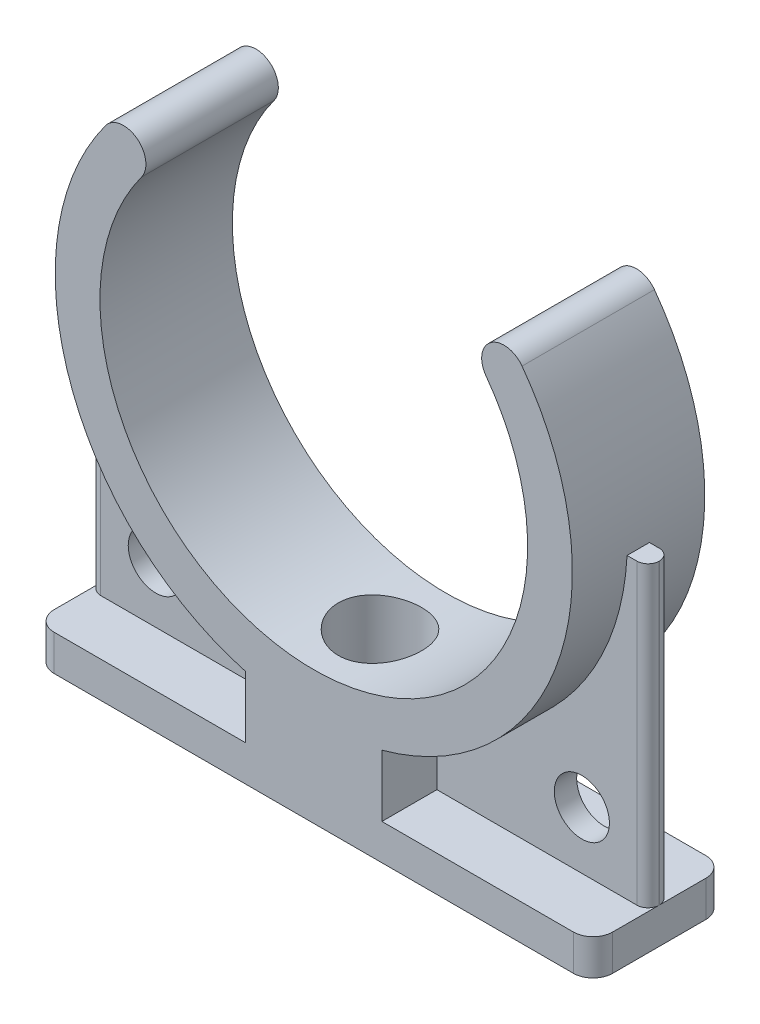
SolidWorks part; units mm, degrees
ref_plane "Front Plane" through (0, 0, 0) normal (0, 0, 1) x (1, 0, 0)
ref_plane "Top Plane" through (0, 0, 0) normal (0, 1, 0) x (1, 0, 0)
ref_plane "Right Plane" through (0, 0, 0) normal (1, 0, 0) x (0, 0, -1)
ref_plane "Plane1" through (0, 0, -1.5875) normal (0, 0, -1) x (-1, 0, 0)
sketch "Sketch1" plane through (0, 0, -1.5875) normal (0, 0, -1) x (-1, 0, 0)
  line L0 (-36.6548, 47.371) -> (36.6548, 47.371)
  arc A0 (36.6548, 47.371) -> (-36.6548, 47.371) centre (0, 49.2507) ccw
extrude "Boss-Extrude1" add sketch "Sketch1" against normal blind 3.175
sketch "Sketch2" plane through (0, 47.371, 0) normal (0, -1, 0) x (1, 0, 0)
  line L0 (36.6548, -1.5875) -> (-36.6548, -1.5875)
  line L1 (-36.6548, -1.5875) -> (-36.6548, 1.5875)
  line L2 (-36.6548, 1.5875) -> (36.6548, 1.5875)
  line L3 (36.6548, 1.5875) -> (36.6548, -1.5875)
extrude "Boss-Extrude2" add sketch "Sketch2" along normal blind 33.528
sketch "Sketch3" plane through (0, 0, -1.5875) normal (0, 0, -1) x (-1, 0, 0)
  line L0 (9.6647, 13.843) -> (-9.6647, 13.843)
  arc A0 (-9.6647, 13.843) -> (9.6647, 13.843) centre (0, 49.2507) cw
extrude "Boss-Extrude3" add sketch "Sketch3" along normal blind 7.8105
sketch "Sketch4" plane through (-36.6548, 0, 0) normal (-1, 0, 0) x (0, 0, 1)
  line L0 (-1.5875, 13.843) -> (-1.5875, 47.371)
  line L1 (-1.5875, 47.371) -> (1.5875, 47.371)
  line L2 (1.5875, 47.371) -> (1.5875, 13.843)
  line L3 (1.5875, 13.843) -> (-1.5875, 13.843)
extrude "Boss-Extrude4" add sketch "Sketch4" along normal blind 2.9819
sketch "Sketch5" plane through (36.6548, 0, 0) normal (1, 0, 0) x (0, 0, -1)
  line L0 (-1.5875, 13.843) -> (-1.5875, 47.371)
  line L1 (-1.5875, 47.371) -> (1.5875, 47.371)
  line L2 (1.5875, 47.371) -> (1.5875, 13.843)
  line L3 (1.5875, 13.843) -> (-1.5875, 13.843)
extrude "Boss-Extrude5" add sketch "Sketch5" along normal blind 2.9819
sketch "Sketch6" plane through (0, 13.843, 0) normal (0, -1, 0) x (1, 0, 0)
  line L0 (-39.6367, 1.5875) -> (39.6367, 1.5875)
  line L1 (39.6367, 1.5875) -> (39.6367, -9.398)
  line L2 (39.6367, -9.398) -> (-39.6367, -9.398)
  line L3 (-39.6367, -9.398) -> (-39.6367, 1.5875)
extrude "Boss-Extrude6" add sketch "Sketch6" along normal blind 13.843
sketch "Sketch7" plane through (0, 13.843, 0) normal (0, 1, 0) x (-1, 0, 0)
  line L0 (-39.6367, -1.5875) -> (-39.6367, -9.398)
  line L1 (-39.6367, -9.398) -> (-9.6647, -9.398)
  line L2 (-9.6647, -9.398) -> (-9.6647, -1.5875)
  line L3 (-9.6647, -1.5875) -> (-39.6367, -1.5875)
extrude "Cut-Extrude1" cut sketch "Sketch7" against normal blind 8.763
sketch "Sketch8" plane through (0, 13.843, 0) normal (0, 1, 0) x (-1, 0, 0)
  line L0 (9.6647, -9.398) -> (39.6367, -9.398)
  line L1 (39.6367, -9.398) -> (39.6367, -1.5875)
  line L2 (39.6367, -1.5875) -> (9.6647, -1.5875)
  line L3 (9.6647, -1.5875) -> (9.6647, -9.398)
extrude "Cut-Extrude2" cut sketch "Sketch8" against normal blind 8.763
sketch "Sketch9" plane through (0, 0, 1.5875) normal (0, 0, 1) x (1, 0, 0)
  line L0 (9.6647, 13.843) -> (9.6647, 5.08)
  line L1 (9.6647, 5.08) -> (39.6367, 5.08)
  line L2 (39.6367, 5.08) -> (39.6367, 0)
  line L3 (39.6367, 0) -> (-39.6367, 0)
  line L4 (-39.6367, 0) -> (-39.6367, 5.08)
  line L5 (-39.6367, 5.08) -> (-9.6647, 5.08)
  line L6 (-9.6647, 5.08) -> (-9.6647, 13.843)
  arc A0 (-9.6647, 13.843) -> (9.6647, 13.843) centre (0, 49.2507) cw
extrude "Boss-Extrude7" add sketch "Sketch9" along normal blind 7.8105
sketch "Sketch10" plane through (0, 0, 9.398) normal (0, 0, 1) x (1, 0, 0)
  arc A0 (-29.562, 71.0037) -> (-24.4475, 67.2402) centre (-27.0048, 69.122) cw
  arc A1 (-24.4475, 67.2402) -> (24.4475, 67.2402) centre (0, 49.2507) cw
  arc A2 (24.4475, 67.2402) -> (29.562, 71.0037) centre (27.0048, 69.122) cw
  arc A3 (29.562, 71.0037) -> (-29.562, 71.0037) centre (0, 49.2507) ccw
extrude "Cut-Extrude3" cut sketch "Sketch10" against normal through all
ref_plane "Plane2" through (0, 49.2507, 0) normal (0, -1, 0) x (1, 0, 0)
sketch "Sketch11" plane through (0, 49.2507, 0) normal (0, -1, 0) x (1, 0, 0)
  line L0 (30.353, 9.398) -> (0, 9.398)
  line L1 (0, 9.398) -> (0, -9.398)
  line L2 (0, -9.398) -> (30.353, -9.398)
  line L3 (30.353, -9.398) -> (30.353, 9.398)
  line L4 (0, 9.398) -> (0, -9.398) construction
revolve "Cut-Revolve1" cut sketch "Sketch11" angle 360 about L4 reverse direction yes
ref_plane "Plane3" through (0, 19.4777, 0) normal (0, 1, 0) x (1, 0, 0)
hole_wizard "Hole1" positions "Sketch13" profile "Sketch12" legacy
sketch "Sketch13" plane through (0, 19.4777, 0) normal (0, 1, 0) x (1, 0, 0)
  point P0 (0, 0)
sketch "Sketch12" plane through (0, 19.4777, 0) normal (1, 0, 0) x (0, 0, 1)
  line L0 (0, 0) -> (0, 19.4777)
  line L1 (0, 19.4777) -> (2.54, 19.4777)
  line L2 (2.54, 19.4777) -> (2.54, 14.1437)
  line L3 (2.54, 14.1437) -> (5.9055, 14.1437)
  line L4 (5.9055, 14.1437) -> (5.9055, 0)
  line L5 (5.9055, 0) -> (0, 0)
  line L6 (0, 110) -> (0, -10) construction
  dimension "Diameter" = 5.08
  dimension "Depth" = 19.4777
  dimension "C-Bore Diameter" = 11.811
  dimension "C-Bore Depth" = 14.1437
hole_wizard "M7 Clearance Hole1" positions "Sketch15" profile "Sketch14" hole size "M7" standard "ANSI Metric"
sketch "Sketch15" plane through (0, 0, -1.5875) normal (0, 0, -1) x (-1, 0, 0)
  point P0 (30.2387, 13.208)
sketch "Sketch14" plane through (-30.2387, 13.208, -1.5875) normal (1, 0, 0) x (0, 1, 0)
  line L0 (0, 0) -> (0, 10.9855)
  line L1 (0, 10.9855) -> (3.9116, 10.9855)
  line L2 (3.9116, 10.9855) -> (3.9116, 0)
  line L5 (3.9116, 0) -> (0, 0)
  line L11 (0, -6.35) -> (0, 107.95) construction
  dimension "Thru Hole Dia." = 7.8232
  dimension "Thru Hole Depth" = 10.9855
hole_wizard "M7 Clearance Hole2" positions "Sketch17" profile "Sketch16" hole size "M7" standard "ANSI Metric"
sketch "Sketch17" plane through (0, 0, 1.5875) normal (0, 0, 1) x (1, 0, 0)
  point P0 (30.2387, 13.208)
sketch "Sketch16" plane through (30.2387, 13.208, 1.5875) normal (1, 0, 0) x (0, -1, 0)
  line L0 (0, 0) -> (0, 10.9855)
  line L1 (0, 10.9855) -> (3.9116, 10.9855)
  line L2 (3.9116, 10.9855) -> (3.9116, 0)
  line L5 (3.9116, 0) -> (0, 0)
  line L11 (0, -6.35) -> (0, 107.95) construction
  dimension "Thru Hole Dia." = 7.8232
  dimension "Thru Hole Depth" = 10.9855
fillet "Fillet1" radius 1.5799 4 edges at (-39.6367, 26.2255, -1.5875) (-39.6367, 26.2255, 1.5875) (39.6367, 26.2255, -1.5875) (39.6367, 26.2255, 1.5875) tangent propagation no
fillet "Fillet2" radius 2.794 4 edges at (39.6367, 2.54, -9.398) (39.6367, 2.54, 9.398) (-39.6367, 2.54, -9.398) (-39.6367, 2.54, 9.398) tangent propagation no
